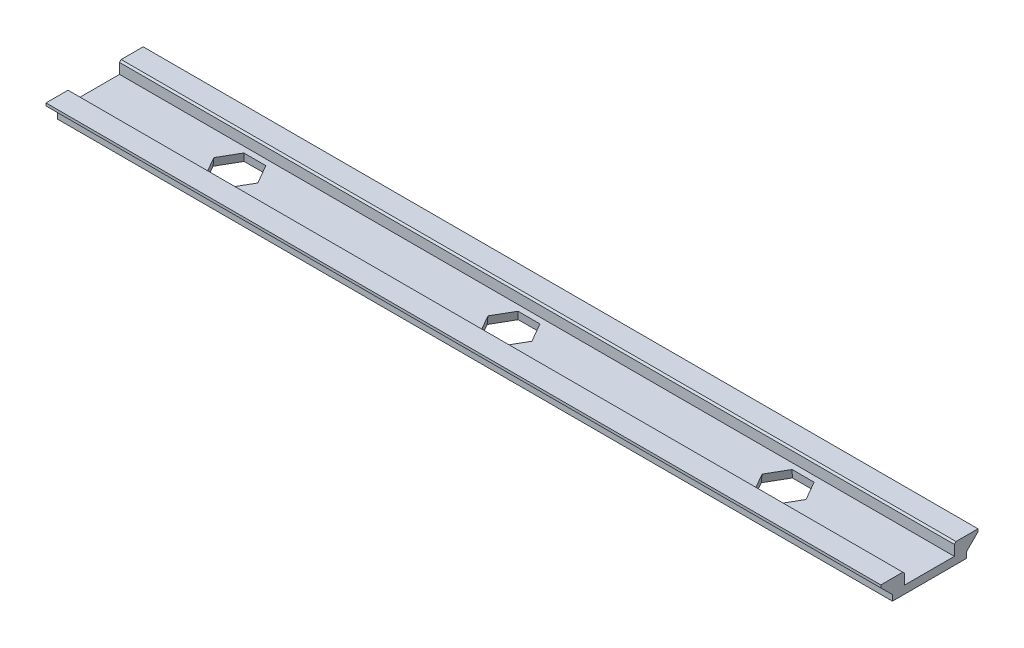
SolidWorks part; units mm, degrees
ref_plane "Front Plane" through (0, 0, 0) normal (0, 0, 1) x (1, 0, 0)
ref_plane "Top Plane" through (0, 0, 0) normal (0, 1, 0) x (1, 0, 0)
ref_plane "Right Plane" through (0, 0, 0) normal (1, 0, 0) x (0, 0, -1)
sketch "Retainer Profile" plane through (0, 0, 0) normal (1, 0, 0) x (0, 0, -1)
  line L1 (-4.65, 2.7923) -> (-4.65, 2.1923) construction
  line L2 (-6.05, 4.1923) -> (-4.65, 2.7923) construction
  line L8 (-6.05, 4.7923) -> (-6.05, 4.1923) construction
  line L9 (-5.05, 4.7923) -> (-6.05, 4.7923) construction
  line L10 (-4.65, 2.7923) -> (-4.65, 2.1923) construction
  line L11 (-6.05, 4.1923) -> (-4.65, 2.7923) construction
  line L23 (0, -28.6883) -> (0, 28.6883) construction
  line L24 (0, -28.6883) -> (0, 28.6883) construction
  line L27 (-6.05, 4.7923) -> (-6.05, 4.1923) construction
  line L28 (-5.05, 4.7923) -> (-6.05, 4.7923) construction
  line L31 (-5.05, 4.5923) -> (-5.85, 4.5923)
  line L32 (-5.85, 4.5923) -> (-5.85, 4.2751)
  line L33 (-5.85, 4.2751) -> (-4.45, 2.8751)
  line L34 (-4.45, 2.8751) -> (-4.45, 2.1923)
  line L35 (-5.05, 4.5923) -> (-3, 4.5923)
  line L36 (-3, 4.5923) -> (-3, 3.1423)
  line L37 (-3, 3.1423) -> (3, 3.1423)
  line L38 (-4.45, 2.1923) -> (4.45, 2.1923)
  line L39 (3, 4.5923) -> (3, 3.1423)
  line L40 (5.05, 4.5923) -> (3, 4.5923)
  line L41 (4.45, 2.8751) -> (4.45, 2.1923)
  line L42 (5.85, 4.2751) -> (4.45, 2.8751)
  line L43 (5.85, 4.5923) -> (5.85, 4.2751)
  line L44 (5.05, 4.5923) -> (5.85, 4.5923)
  point P15 (0, 2.1923)
  point P16 (0, 3.1423)
  dimension "D3" = 3
  dimension "D1" = 0.2
  dimension "D2" = 1.45
extrude "Boss-Extrude1" add sketch "Retainer Profile" along normal mid plane 100.5
sketch "Sketch3" plane through (0, 4.5923, 0) normal (0, 1, 0) x (1, 0, 0)
  line L0 (50.25, -5.05) -> (50.25, 5.05) construction
  line L1 (35.25, 0) -> (34, 2.1651)
  line L2 (34, 2.1651) -> (31.5, 2.1651)
  line L3 (31.5, 2.1651) -> (30.25, 0)
  line L4 (30.25, 0) -> (31.5, -2.1651)
  line L5 (31.5, -2.1651) -> (34, -2.1651)
  line L6 (34, -2.1651) -> (35.25, 0)
  line L7 (2.25, 0) -> (1, 2.1651)
  line L8 (1, 2.1651) -> (-1.5, 2.1651)
  line L9 (-1.5, 2.1651) -> (-2.75, 0)
  line L10 (-2.75, 0) -> (-1.5, -2.1651)
  line L11 (-1.5, -2.1651) -> (1, -2.1651)
  line L12 (1, -2.1651) -> (2.25, 0)
  line L13 (-30.75, 0) -> (-32, 2.1651)
  line L14 (-32, 2.1651) -> (-34.5, 2.1651)
  line L15 (-34.5, 2.1651) -> (-35.75, 0)
  line L16 (-35.75, 0) -> (-34.5, -2.1651)
  line L17 (-34.5, -2.1651) -> (-32, -2.1651)
  line L18 (-32, -2.1651) -> (-30.75, 0)
  circle A0 centre (32.75, 0) radius 2.1651 construction
  circle A1 centre (-0.25, 0) radius 2.1651 construction
  circle A2 centre (-33.25, 0) radius 2.1651 construction
  dimension "D1" = 5
  dimension "D2" = 15
  dimension "D3" = 3
extrude "Cut-Extrude2" cut sketch "Sketch3" against normal through all draft 5 draft outward yes
chamfer "Chamfer1" distance 0.2 angle 45 2 edges at (0, 4.5923, 3) (0, 4.5923, -3)
